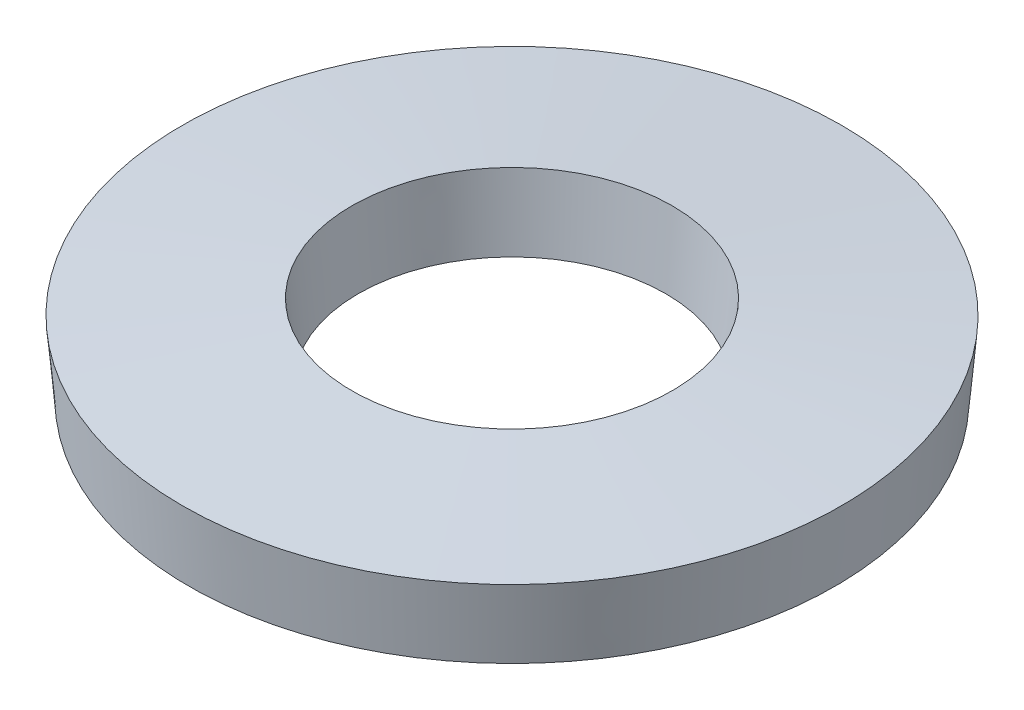
SolidWorks part; units mm, degrees
ref_plane "Front" through (0, 0, 0) normal (0, 0, 1) x (1, 0, 0)
ref_plane "Top" through (0, 0, 0) normal (0, 1, 0) x (1, 0, 0)
ref_plane "Right" through (0, 0, 0) normal (1, 0, 0) x (0, 0, -1)
sketch "Sketch1" plane through (0, 0, 0) normal (0, 0, 1) x (1, 0, 0)
  line L0 (8.8243, 0) -> (4.2, 0.4077)
  line L1 (4.2, 0.4077) -> (4.3757, 2.4)
  line L2 (4.3757, 2.4) -> (9, 1.9923)
  line L3 (9, 1.9923) -> (8.8243, 0)
  line L4 (0, 0) -> (0, 2.4) construction
  line L5 (-9, 1.9923) -> (-8.8243, 0) construction
  line L6 (-4.3757, 2.4) -> (-9, 1.9923) construction
  line L7 (-4.2, 0.4077) -> (-4.3757, 2.4) construction
  line L8 (-8.8243, 0) -> (-4.2, 0.4077) construction
  point P5 (4.2878, 1.4039)
  point P8 (-4.2878, 1.4039)
  dimension "D1" = 4.6423
  dimension "ID" = 8.4
  dimension "OD" = 18
  dimension "Thickness" = 2
  dimension "Height" = 2.4
revolve "Revolve1" add sketch "Sketch1" angle 360 about L4
sketch "Sketch15" plane through (0, 0, 0) normal (0, 1, 0) x (1, 0, 0)
  circle A0 centre (0, 0) radius 9
  circle A1 centre (0, 0) radius 4.2
ref_axis "Center Axis 1" through (0, 0, 0) along (0, 1, 0)
ref_plane "Contact Plane 1" through (0, 2.4, 0) normal (0, 1, 0) x (-1, 0, 0)
ref_plane "Contact Plane 2" through (0, 0, 0) normal (0, 1, 0) x (-1, 0, 0)
